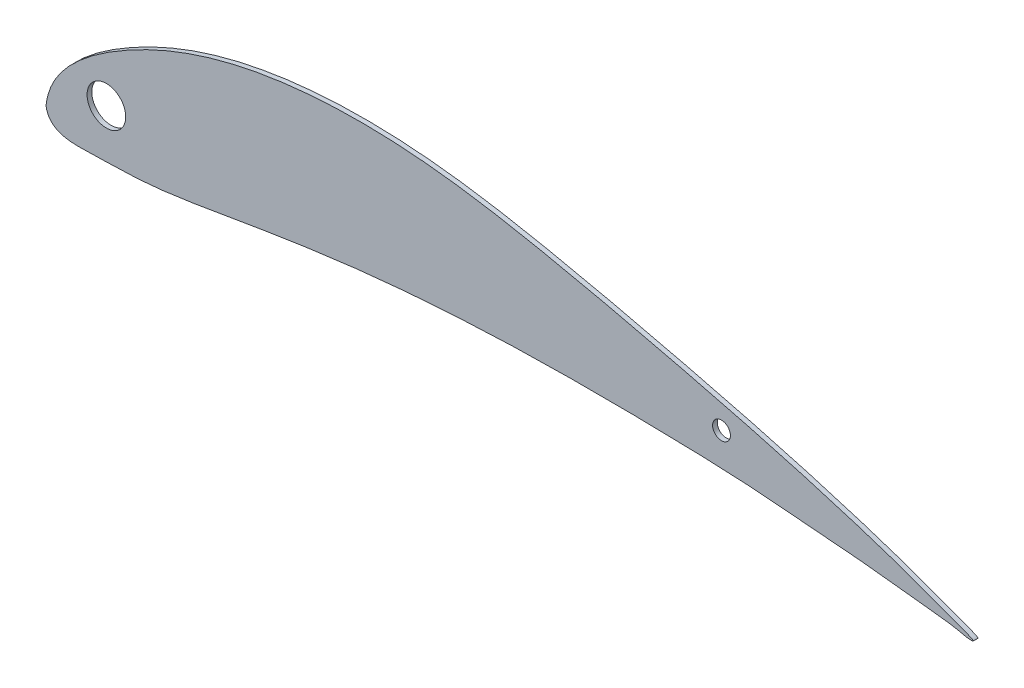
SolidWorks part; units mm, degrees
material "Balsa"
ref_plane "Front Plane" through (0, 0, 0) normal (0, 0, 1) x (1, 0, 0)
ref_plane "Top Plane" through (0, 0, 0) normal (0, 1, 0) x (1, 0, 0)
ref_plane "Right Plane" through (0, 0, 0) normal (1, 0, 0) x (0, 0, -1)
sketch "Sketch1" plane through (0, 0, 0) normal (0, 0, 1) x (1, 0, 0)
  spline S0 degree 3 poles (0.0006, 0.0001) (0.8106, 7.3592) (8.6491, 17.8566) (26.2867, 29.9752) (52.1111, 42.0692) (89.5976, 49.2908) (131.4008, 47.8848) (173.2567, 40.0411) (217.9611, 29.613) (256.9521, 19.5289) (290.3598, 8.711) (301.2732, 4.3828) (314.8169, -0.5162) (309.8463, 0.0001) knots 0 0 0 0 0.060864 0.113688 0.188609 0.312909 0.448482 0.557612 0.691544 0.852438 0.929756 0.976058 1 1 1 1
  spline S1 degree 3 poles (309.8463, 0.0001) (303.9568, 1.471) (293.9895, 2.094) (276.264, 4.5144) (260.8463, 5.4274) (235.8588, 7.8703) (205.1014, 8.8381) (157.7186, 9.0307) (110.4973, 6.1815) (66.5062, -0.5867) (36.4547, -6.0985) (15.3166, -6.1891) (1.2307, -6.9241) (0.0006, 0.0001) knots 0 0 0 0 0.057787 0.095275 0.171021 0.205339 0.335319 0.464904 0.658702 0.785512 0.893517 0.943092 1 1 1 1
extrude "Boss-Extrude1" add sketch "Sketch1" along normal blind 1.5875
sketch "Sketch2" plane through (0, 0, 1.5875) normal (0, 0, 1) x (1, 0, 0)
  line L0 (227.2963, 19.0501) -> (20.32, 10.16) construction
  line L1 (20.32, 10.16) -> (227.2963, 10.16) construction
  line L2 (227.2963, 10.16) -> (227.2963, 19.0501) construction
  circle A0 centre (20.32, 10.16) radius 6.5
  circle A1 centre (227.2963, 19.0501) radius 3
  dimension "D2" = 13
  dimension "D3" = 6
  dimension "D6" = 20.32
  dimension "D1" = 82.55
  dimension "D4" = 19.05
  dimension "D5" = 10.16
extrude "Cut-Extrude1" cut sketch "Sketch2" against normal through all
sketch "Sketch3" plane through (0, 0, 0) normal (0, 0, -1) x (-1, 0, 0)
  line L0 (-309.8463, 0.0001) -> (-259.6129, 0.0001)
